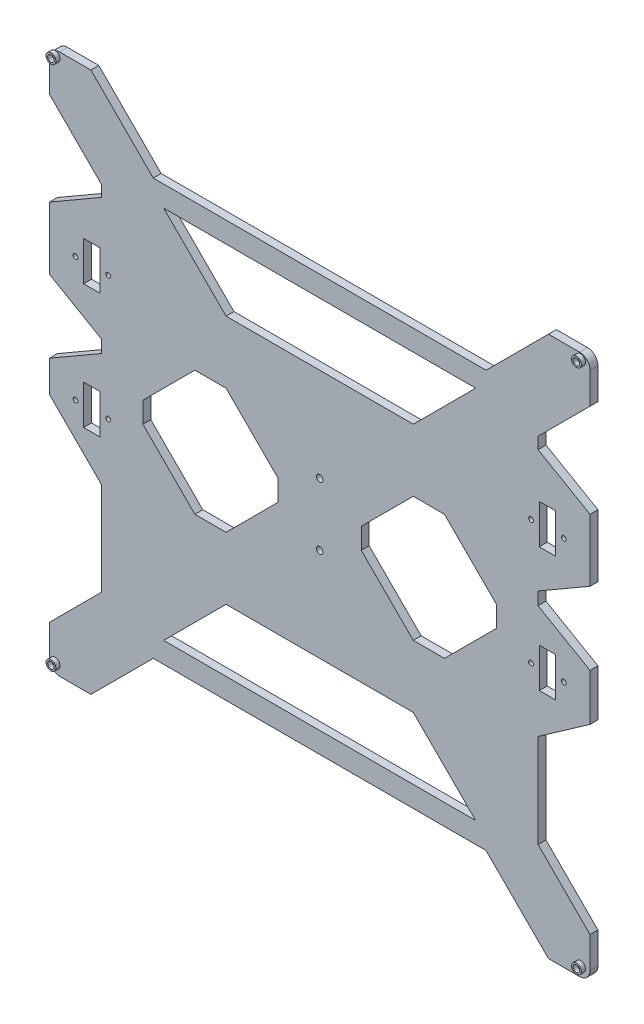
SolidWorks part; units mm, degrees
material "5052-H32"
ref_plane "Front Plane" through (0, 0, 0) normal (0, 0, 1) x (1, 0, 0)
ref_plane "Top Plane" through (0, 0, 0) normal (0, 1, 0) x (1, 0, 0)
ref_plane "Right Plane" through (0, 0, 0) normal (1, 0, 0) x (0, 0, -1)
sketch "Model" plane through (0, 0, 0) normal (0, 0, 1) x (1, 0, 0)
  line L0 (38.5361, 132.6139) -> (38.5361, 132.4727)
  line L1 (38.5361, -178.6774) -> (38.5361, -178.7219)
  line L2 (-253.5639, -197.5861) -> (-253.5639, -197.7273)
  line L3 (-290.6813, -31.2683) -> (-258.9313, -12.9374)
  line L4 (-258.9313, -82.0683) -> (-258.9313, -139.2183)
  line L5 (38.5361, 132.6139) -> (38.5361, 132.4727)
  line L6 (38.5361, -178.6774) -> (38.5361, -178.7219)
  line L7 (7.7687, -139.2183) -> (7.7687, -82.0683)
  line L8 (39.5187, -59.8367) -> (39.5187, -31.2683)
  line L9 (-23.9813, 95.7317) -> (-227.1813, 95.7317)
  line L10 (-290.6813, 108.4317) -> (-258.9313, 76.6817)
  line L11 (-30.3313, -145.5683) -> (-68.4313, -107.4683)
  line L12 (-23.9813, -158.2683) -> (14.1187, -196.3683)
  line L13 (39.5187, 108.4317) -> (39.5187, 127.4817)
  line L14 (-227.1813, 95.7317) -> (-265.2813, 133.8317)
  line L15 (-220.8313, 83.0317) -> (-182.7313, 44.9317)
  line L16 (-274.6813, -45.4288) -> (-254.6813, -45.4288) construction
  line L17 (39.5187, -170.9683) -> (7.7687, -139.2183)
  line L18 (-265.2813, -196.3683) -> (-227.1813, -158.2683)
  line L19 (-182.7313, -107.4683) -> (-68.4313, -107.4683)
  line L20 (-264.6813, -45.4288) -> (-264.6813, -43.5832) construction
  line L21 (7.7687, 76.6817) -> (39.5187, 108.4317)
  line L22 (-23.9813, 95.7317) -> (14.1187, 133.8317)
  line L23 (-30.3313, 83.0317) -> (-68.4313, 44.9317)
  line L24 (39.5187, -31.2683) -> (7.7687, -12.9374)
  line L25 (-258.9313, -139.2183) -> (-290.6813, -170.9683)
  line L26 (-182.7313, 44.9317) -> (-68.4313, 44.9317)
  line L27 (-220.8313, -145.5683) -> (-182.7313, -107.4683)
  line L28 (-220.8313, -145.5683) -> (-30.3313, -145.5683)
  line L29 (-258.9313, -82.0683) -> (-290.6813, -50.3183)
  line L30 (-290.6813, -31.2683) -> (-290.6813, -50.3183)
  line L31 (-274.6813, -43.9683) -> (-274.6813, -31.2683) construction
  line L32 (-258.9313, -12.9374) -> (-258.9313, -5.1492)
  line L33 (-201.7813, -69.3683) -> (-233.5313, -37.6183)
  line L34 (-182.7313, -69.3683) -> (-201.7813, -69.3683)
  line L35 (7.7687, -12.9374) -> (7.7687, -5.1492)
  line L36 (7.7687, -5.1492) -> (39.5187, 13.1817)
  line L37 (-150.9813, -37.6183) -> (-182.7313, -69.3683)
  line L38 (39.5187, -59.8367) -> (10.4646, -80.1806)
  line L39 (10.4646, -80.1806) -> (7.7687, -82.0683)
  line L40 (-100.1813, -37.6183) -> (-100.1813, -24.9183)
  line L41 (-150.9813, -37.6183) -> (-150.9813, -24.9183)
  line L42 (-150.9813, -24.9183) -> (-182.7313, 6.8317)
  line L43 (-182.7313, 6.8317) -> (-201.7813, 6.8317)
  line L44 (-201.7813, 6.8317) -> (-233.5313, -24.9183)
  line L45 (-233.5313, -24.9183) -> (-233.5313, -37.6183)
  line L46 (-17.6313, -24.9183) -> (-17.6313, -37.6183)
  line L47 (-49.3813, 6.8317) -> (-17.6313, -24.9183)
  line L48 (-220.8313, 83.0317) -> (-30.3313, 83.0317)
  line L49 (-68.4313, 6.8317) -> (-49.3813, 6.8317)
  line L50 (-100.1813, -24.9183) -> (-68.4313, 6.8317)
  line L51 (-100.1813, -37.6183) -> (-68.4313, -69.3683)
  line L52 (-68.4313, -69.3683) -> (-49.3813, -69.3683)
  line L53 (-49.3813, -69.3683) -> (-17.6313, -37.6183)
  line L54 (39.5187, 13.1817) -> (39.5187, 51.2817)
  line L55 (39.5187, 51.2817) -> (7.7687, 69.6126)
  line L56 (7.7687, 69.6126) -> (7.7687, 76.6817)
  line L57 (-258.9313, -5.1492) -> (-290.6813, 13.1817)
  line L58 (-265.2813, -196.3683) -> (-284.3313, -196.3683)
  line L59 (-290.6813, -190.0183) -> (-290.6813, -170.9683)
  line L60 (-290.6813, 108.4317) -> (-290.6813, 127.4817)
  line L61 (-284.3313, 133.8317) -> (-265.2813, 133.8317)
  line L62 (14.1187, 133.8317) -> (33.1687, 133.8317)
  line L63 (-290.6813, 13.1817) -> (-290.6813, 51.2817)
  line L64 (39.5187, -170.9683) -> (39.5187, -190.0183)
  line L65 (33.1687, -196.3683) -> (14.1187, -196.3683)
  line L66 (-258.9313, 76.6817) -> (-258.9313, 69.6126)
  line L67 (-258.9313, 69.6126) -> (-290.6813, 51.2817)
  line L68 (-274.6813, 30.5682) -> (-254.6813, 30.5682) construction
  line L69 (-254.6813, 30.5682) -> (23.5187, 30.5682) construction
  line L70 (23.5187, 30.5682) -> (23.5187, -45.4288) construction
  line L71 (-227.1813, -158.2683) -> (-23.9813, -158.2683)
  line L72 (38.5361, -178.6774) -> (38.5361, -178.7219)
  line L73 (3.5187, 30.5682) -> (3.5187, -45.4288) construction
  line L74 (-227.1813, -158.2683) -> (-23.9813, -158.2683)
  line L75 (38.5361, -178.6774) -> (38.5361, -178.7219)
  line L76 (-274.6813, 30.5682) -> (-274.6813, -45.4288) construction
  line L77 (-125.5813, 95.7317) -> (-125.5813, -158.2683) construction
  line L78 (-290.6813, -31.2683) -> (39.5187, -31.2683) construction
  arc A0 (33.1687, -196.3683) -> (39.5187, -190.0183) centre (33.1687, -190.0183) ccw
  arc A1 (-290.6813, -190.0183) -> (-284.3313, -196.3683) centre (-284.3313, -190.0183) ccw
  arc A2 (-290.6813, 127.4817) -> (-284.3313, 133.8317) centre (-284.3313, 127.4817) cw
  arc A3 (33.1687, 133.8317) -> (39.5187, 127.4817) centre (33.1687, 127.4817) cw
  circle A4 centre (-287.1253, -190.6025) radius 1.4605
  circle A5 centre (33.7529, -190.6025) radius 1.4605
  circle A6 centre (33.7529, 130.2757) radius 1.4605
  circle A7 centre (-287.1253, 130.2757) radius 1.4605
  circle A8 centre (-274.6813, -45.4288) radius 1.4605
  circle A9 centre (-254.6813, -45.4288) radius 1.4605
  circle A10 centre (23.5187, -45.4288) radius 1.4605
  circle A11 centre (3.5187, -45.4288) radius 1.4605
  circle A12 centre (23.5187, 30.5682) radius 1.4605
  circle A13 centre (3.5187, 30.5682) radius 1.4605
  circle A14 centre (-254.6813, 30.5682) radius 1.4605
  circle A15 centre (-274.6813, 30.5682) radius 1.4605
  circle A16 centre (-125.5813, -12.2183) radius 2
  circle A17 centre (-125.5813, -50.3183) radius 2
  point P72 (-125.5813, -31.2683)
  point P114 (-125.5813, 83.0317)
  point P120 (-233.5313, -31.2683)
  point P129 (-150.9813, -31.2683)
  point P149 (-125.5813, 44.9317)
  point P156 (-17.6313, -31.2683)
  dimension "D28" = 6.35
  dimension "D29" = 6.35
  dimension "D30" = 6.35
  dimension "D31" = 6.35
  dimension "D35" = 2.921
  dimension "D36" = 2.921
  dimension "D37" = 2.921
  dimension "D38" = 2.921
  dimension "D53" = 2.921
  dimension "D54" = 2.921
  dimension "D56" = 4
  dimension "D57" = 4
  dimension "D1" = 330.2
  dimension "D2" = 330.2
  dimension "D3" = 135
  dimension "D4" = 135
  dimension "D5" = 38.1
  dimension "D6" = 135
  dimension "D7" = 120
  dimension "D8" = 19.05
  dimension "D9" = 135
  dimension "D10" = 19.05
  dimension "D11" = 31.75
  dimension "D12" = 190.5
  dimension "D13" = 114.3
  dimension "D14" = 38.1
  dimension "D15" = 114.3
  dimension "D16" = 135
  dimension "D17" = 6.35
  dimension "D18" = 38.1
  dimension "D19" = 135
  dimension "D20" = 135
  dimension "D21" = 6.35
  dimension "D22" = 19.05
  dimension "D23" = 25.4
  dimension "D24" = 50.8
  dimension "D25" = 120
  dimension "D26" = 135
  dimension "D27" = 127
  dimension "D32" = 19.05
  dimension "D33" = 19.05
  dimension "D34" = 19.05
  dimension "D39" = 120
  dimension "D40" = 19.05
  dimension "D41" = 120
  dimension "D42" = 120
  dimension "D43" = 50.8
  dimension "D44" = 19.05
  dimension "D45" = 31.75
  dimension "D46" = 125
  dimension "D47" = 320.8782
  dimension "D48" = 320.8782
  dimension "D49" = 3.556
  dimension "D50" = 3.556
  dimension "D51" = 20
  dimension "D52" = 26
  dimension "D55" = 12.7
  dimension "D58" = 38.1
  dimension "D59" = 19.05
  dimension "D60" = 82.55
  dimension "D61" = 38.1
  dimension "D63" = 120
  dimension "D64" = 38.1
  dimension "D65" = 82.55
  dimension "D67" = 75.997
extrude "Boss-Extrude1" add sketch "Model" along normal mid plane 4.826 contours A3 L62 L22 L9 L14 L61 A2 L60 L10 L30 L29 L4 L25 L59 A1 L58 L18 L71 L12 L65 A0 L64 L17 L7 L39 L38 L8 L21 L13 A17 A16 A14 A13 A12 A10 A9 region at (-125.199, -28.2686, 0)
sketch "Sketch1" plane through (0, 0, 2.413) normal (0, 0, 1) x (1, 0, 0)
  line L0 (23.5187, 30.5682) -> (23.5187, 17.7506) construction
  line L1 (-269.6813, -33.4288) -> (-259.6813, -33.4288)
  line L2 (-269.6813, -33.4288) -> (-269.6813, -57.4288)
  line L3 (-269.6813, -57.4288) -> (-259.6813, -57.4288)
  line L4 (-259.6813, -33.4288) -> (-259.6813, -57.4288)
  line L5 (-269.6813, 42.5712) -> (-259.6813, 42.5712)
  line L6 (-269.6813, 42.5712) -> (-269.6813, 18.5712)
  line L7 (-269.6813, 18.5712) -> (-259.6813, 18.5712)
  line L8 (-259.6813, 42.5712) -> (-259.6813, 18.5712)
  line L9 (8.5187, 42.5712) -> (18.5187, 42.5712)
  line L10 (8.5187, 42.5712) -> (8.5187, 18.5712)
  line L11 (8.5187, 18.5712) -> (18.5187, 18.5712)
  line L12 (18.5187, 42.5712) -> (18.5187, 18.5712)
  line L13 (8.5187, -33.4288) -> (18.5187, -33.4288)
  line L14 (8.5187, -33.4288) -> (8.5187, -57.4288)
  line L15 (8.5187, -57.4288) -> (18.5187, -57.4288)
  line L16 (18.5187, -33.4288) -> (18.5187, -57.4288)
  circle A1 centre (-274.6813, -45.4288) radius 1.4605 construction
  circle A5 centre (-274.6813, 30.5682) radius 1.4605 construction
  circle A8 centre (23.5187, 30.5682) radius 1.4605 construction
  circle A9 centre (23.5187, -45.4288) radius 1.4605 construction
  point P20 (13.5187, 42.5712)
  dimension "D3" = 12
  dimension "D4" = 5
  dimension "D5" = 10
  dimension "D8" = 100
  dimension "D11" = 100
  dimension "D15" = 12
  dimension "D1" = 10
  dimension "D2" = 24
  dimension "D6" = 24
  dimension "D7" = 5
  dimension "D9" = 24
  dimension "D10" = 5
  dimension "D12" = 10
  dimension "D13" = 10
  dimension "D14" = 24
  dimension "D16" = 5
extrude "Cut-Extrude1" cut sketch "Sketch1" against normal blind 10
sketch "Sketch2" plane through (0, 0, 2.413) normal (0, 0, 1) x (1, 0, 0)
  circle A0 centre (33.7529, -190.6025) radius 3
  circle A1 centre (33.7529, -190.6025) radius 2
  circle A2 centre (-287.1253, -190.6025) radius 2
  circle A3 centre (-287.1253, -190.6025) radius 3
  circle A4 centre (-287.1253, 130.2757) radius 2
  circle A5 centre (-287.1253, 130.2757) radius 3
  circle A6 centre (33.7529, 130.2757) radius 2
  circle A7 centre (33.7529, 130.2757) radius 3
  dimension "D1" = 6
  dimension "D2" = 4
extrude "Boss-Extrude2" add sketch "Sketch2" along normal blind 2.54
